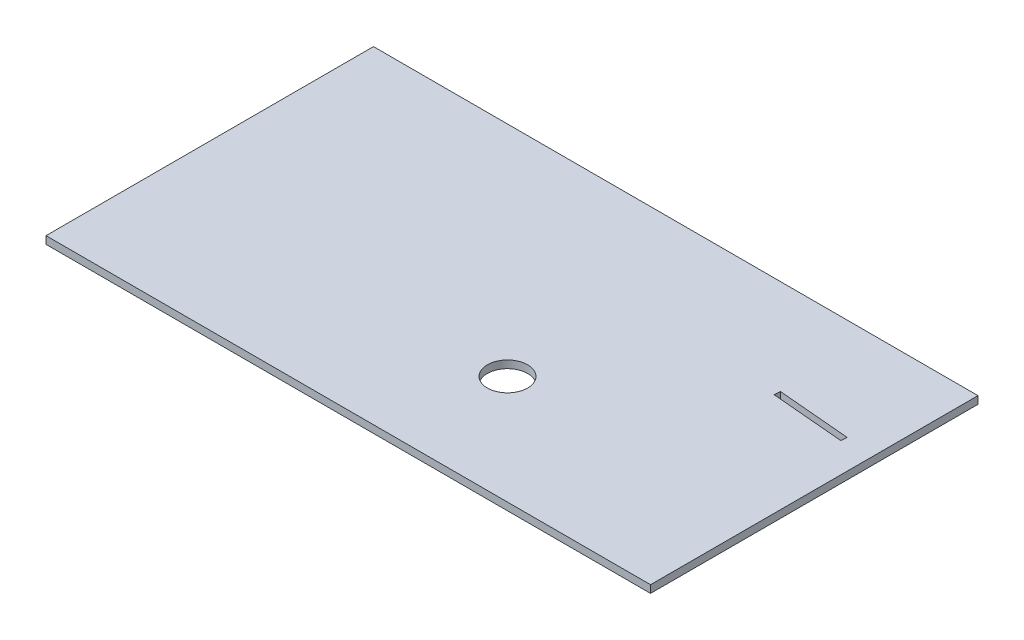
SolidWorks part; units mm, degrees
material "Particle Board"
ref_plane "Front Plane" through (0, 0, 0) normal (0, 0, 1) x (1, 0, 0)
ref_plane "Top Plane" through (0, 0, 0) normal (0, 1, 0) x (1, 0, 0)
ref_plane "Right Plane" through (0, 0, 0) normal (1, 0, 0) x (0, 0, -1)
sketch "Sketch3" plane through (0, 0, 0) normal (0, 1, 0) x (1, 0, 0)
  line L1 (0, 0) -> (-839.8654, 0) construction
  line L2 (0, 0) -> (-451.1992, 260.5) construction
  line L5 (-524, 0) -> (-525.5875, 0)
  line L6 (277.6777, 444.3772) -> (277.6777, 446.248)
  circle A0 centre (0, 0) radius 254 construction
  arc A3 (277.6777, 444.3772) -> (-524, 0) centre (0, 0) ccw
  arc A4 (277.6777, 446.248) -> (-525.5875, 0) centre (0, 0) ccw
  arc A5 (278.5189, 445.7235) -> (-525.5875, 0) centre (0, 0) ccw construction
  dimension "D1" = 524
  dimension "D2" = 1.5875
  dimension "D4" = 122
  dimension "D5" = 508
  dimension "D3" = 30
extrude "Boss-Extrude1" add sketch "Sketch3" along normal blind 50.8
sketch "Sketch4" plane through (0, 50.8, 0) normal (0, 1, 0) x (1, 0, 0)
  line L5 (-889, 551.088) -> (635, 551.088)
  line L6 (-889, 551.088) -> (-889, -274.412)
  line L7 (-889, -274.412) -> (635, -274.412)
  line L8 (635, 551.088) -> (635, -274.412)
  dimension "D1" = 274.412
  dimension "D2" = 1524
  dimension "D3" = 825.5
  dimension "D4" = 635
extrude "Boss-Extrude2" add sketch "Sketch4" along normal blind 19.05
hole_wizard "Ø20.0mm Dowel Hole1" positions "Sketch6" profile "Sketch7" hole size "Ø20.0" standard "ANSI Metric" end condition through all
sketch "Sketch6" plane through (0, 50.8, 0) normal (0, -1, 0) x (-1, 0, 0)
  point P0 (0, 0)
sketch "Sketch7" plane through (0, 50.8, 0) normal (1, 0, 0) x (0, 0, -1)
  line L0 (0, 0) -> (0, 19.05)
  line L1 (0, 19.05) -> (50.8, 19.05)
  line L2 (50.8, 19.05) -> (50.8, 0)
  line L5 (50.8, 0) -> (0, 0)
  line L11 (0, -6.35) -> (0, 107.95) construction
  dimension "Thru Hole Dia." = 101.6
  dimension "Thru Hole Depth" = 19.05
ref_plane "Plane1" through (0, 0, 268.062) normal (0, 0, 1) x (1, 0, 0)
sketch "Sketch8" plane through (0, 0, 0) normal (0, 0, 1) x (1, 0, 0)
  line L0 (-524, 50.8) -> (-524, 0) construction
  line L1 (-525.5875, 50.8) -> (-524, 50.8)
  line L2 (-525.5875, 50.8) -> (-525.5875, 0)
  line L3 (-525.5875, 0) -> (-524, 0)
  line L4 (-524, 50.8) -> (-524, 0)
  line L5 (-525.5875, 50.8) -> (-525.5875, 0) construction
  line L6 (-525.5875, 0) -> (-524, 0) construction
  line L7 (-525.5875, 50.8) -> (-524, 50.8) construction
extrude "Boss-Extrude3" add sketch "Sketch8" along normal blind 204
sketch "Sketch9" plane through (0, 50.8, 0) normal (0, -1, 0) x (-1, 0, 0)
  line L0 (-377.0113, 311.0667) -> (-561.3073, 294.9429)
  line L1 (-561.3073, 294.9429) -> (-560, 280)
  line L2 (-560, 280) -> (-375.704, 296.1238)
  line L3 (-375.704, 296.1238) -> (-377.0113, 311.0667)
  line L6 (0, 0) -> (-635, 0) construction
  line L7 (-635, -274.412) -> (-635, 551.088) construction
  dimension "D1" = 185
  dimension "D2" = 15
  dimension "D3" = 5
  dimension "D4" = 560
  dimension "D5" = 280
extrude "Cut-Extrude1" cut sketch "Sketch9" against normal through all
sketch "Sketch10" plane through (0, 69.85, 0) normal (0, -1, 0) x (-1, 0, 0)
  line L0 (0, 0) -> (-545.6, 0) construction
  line L1 (0, 0) -> (277.6777, 444.3772) construction
  line L2 (0, 0) -> (195.5256, 509.3615) construction
  line L3 (0, 0) -> (94.7424, 537.3111) construction
  circle A0 centre (0, 0) radius 545.6 construction
  dimension "D1" = 11
  dimension "D2" = 11
ref_axis "WHEEL CENTER" through (-565.7508, 50.8, 0) along (1, 0, 0)
ref_plane "BASE CENTER" through (-127, 0, 0) normal (1, 0, 0) x (0, 0, -1)
sketch "Sketch11" plane through (0, 50.8, 0) normal (0, -1, 0) x (1, 0, 0)
  line L0 (240.5176, 138.2676) -> (268.3331, 149.5058)
  line L1 (268.3331, 149.5058) -> (296.8782, 78.8544)
  line L2 (296.8782, 78.8544) -> (269.0626, 67.6162)
  line L3 (269.0626, 67.6162) -> (240.5176, 138.2676)
  line L4 (-561.4964, -185.7671) -> (-532.9514, -256.4185)
  line L5 (-532.9514, -256.4185) -> (-505.1359, -245.1803)
  line L6 (-505.1359, -245.1803) -> (-533.6809, -174.5289)
  line L7 (-533.6809, -174.5289) -> (-561.4964, -185.7671)
  line L8 (-889, -259.242) -> (635, -259.242)
  line L9 (635, 274.412) -> (635, -551.088) construction
  line L10 (-889, -551.088) -> (-889, 274.412) construction
  line L11 (635, -551.088) -> (-889, -551.088) construction
  dimension "D1" = 30
  dimension "D2" = 30
  dimension "D3" = 291.846
